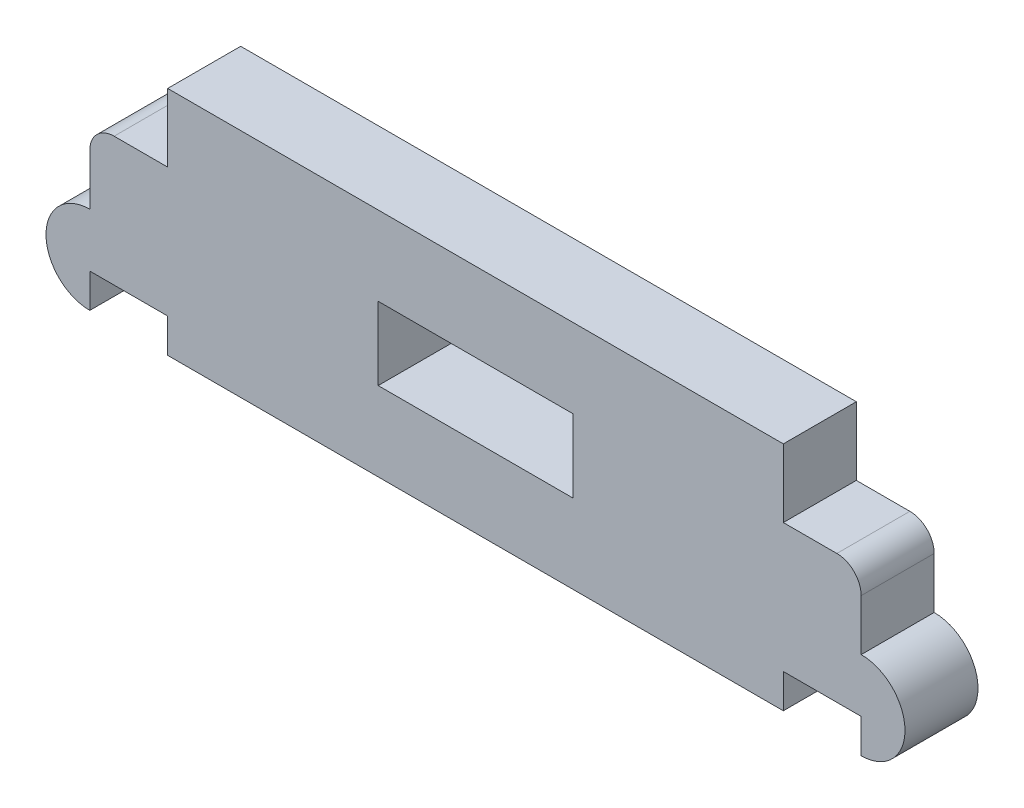
SolidWorks part; units mm, degrees
material "Acrílico (médio-alto impacto)"
ref_plane "Plano frontal" through (0, 0, 0) normal (0, 0, 1) x (1, 0, 0)
ref_plane "Plano superior" through (0, 0, 0) normal (0, 1, 0) x (1, 0, 0)
ref_plane "Plano direito" through (0, 0, 0) normal (1, 0, 0) x (0, 0, -1)
sketch "Base" plane through (0, 0, 0) normal (0, 0, 1) x (1, 0, 0)
  line L1 (-12.65, -4.75) -> (12.65, -4.75)
  line L2 (-12.65, -4.75) -> (-12.65, 4.75)
  line L3 (-12.65, 4.75) -> (12.65, 4.75)
  line L4 (12.65, -4.75) -> (12.65, 4.75)
  line L5 (0, 4.75) -> (0, -4.75) construction
  line L6 (-12.65, 0) -> (12.65, 0) construction
  point P0 (0, 0)
  dimension "D1" = 25.3
  dimension "D2" = 9.5
sketch "Esboço2" plane through (0, 0, 0) normal (0, 0, 1) x (1, 0, 0)
  line L0 (-12.65, -3.35) -> (-15.85, -3.35)
  line L1 (-12.65, -4.75) -> (-12.65, 4.75) construction
  line L2 (-15.85, -3.35) -> (-15.85, -4.75)
  line L3 (-15.85, -1.15) -> (-15.85, 1.95)
  line L4 (-15.85, 1.95) -> (-12.65, 1.95)
  line L5 (-12.65, -4.75) -> (12.65, -4.75) construction
  line L6 (-12.65, 1.95) -> (-12.65, -3.35)
  line L7 (0, 4.75) -> (0, -4.75) construction
  line L8 (-12.65, 4.75) -> (12.65, 4.75) construction
  arc A0 (-15.85, -4.75) -> (-15.85, -1.15) centre (-15.85, -2.95) cw
  dimension "D6" = 35.3
  dimension "D1" = 5.3
  dimension "D2" = 3.2
  dimension "D3" = 6.7
  dimension "D4" = 3.6
  dimension "D5" = 9.5
sketch "Esboço4" plane through (0, 0, 0) normal (0, 0, 1) x (1, 0, 0)
  line L1 (-4, -1.5) -> (4, -1.5)
  line L2 (-4, -1.5) -> (-4, 1.5)
  line L3 (-4, 1.5) -> (4, 1.5)
  line L4 (4, -1.5) -> (4, 1.5)
  line L5 (0, 1.5) -> (0, -1.5) construction
  line L6 (-4, 0) -> (4, 0) construction
  dimension "D1" = 8
  dimension "D2" = 3
extrude "Ressalto-extrusão1" add sketch "Base" along normal blind 3
extrude "Corte-extrusão1" cut sketch "Esboço4" along normal through all
extrude "Ressalto-extrusão2" add sketch "Esboço2" along normal through all
fillet "Filete1" radius 1 1 edges at (-15.85, 1.95, 1.5)
mirror "Espelhar1" about plane through (0, 0, 0) normal (1, 0, 0) of "Filete1", "Ressalto-extrusão2"
sketch "Rota" plane through (0, 0, 0) normal (0, 1, 0) x (1, 0, 0)
  line L0 (0, 0) -> (0, -3) construction
  line L1 (12.65, -3) -> (-12.65, -3) construction
other "PontoR1"
other "PontoR2"
ref_axis "Eixo1" through (0, 0, 0) along (0, 0, 1)
